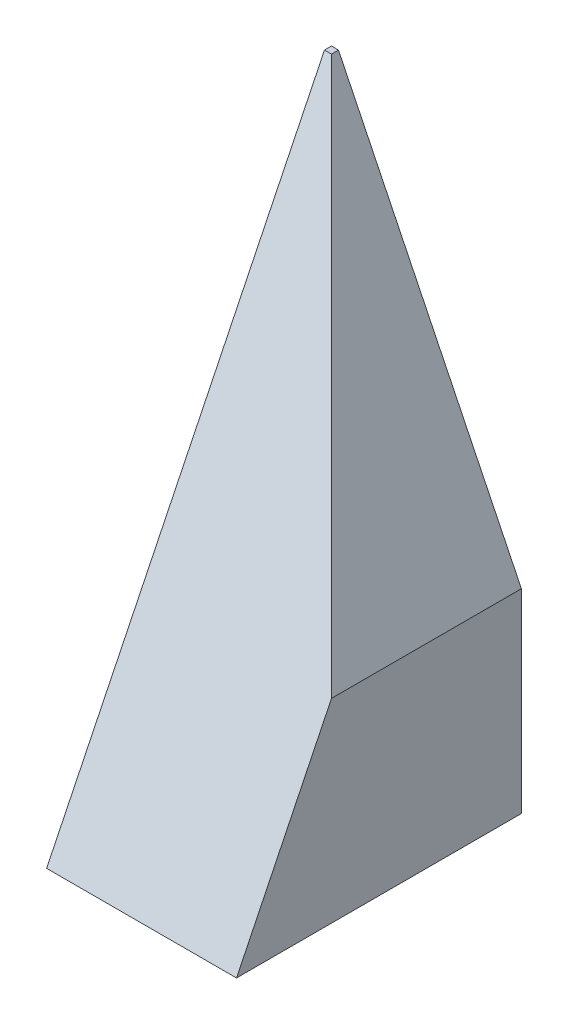
SolidWorks part; units mm, degrees
ref_plane "Front" through (0, 0, 0) normal (0, 0, 1) x (1, 0, 0)
ref_plane "Top" through (0, 0, 0) normal (0, 1, 0) x (1, 0, 0)
ref_plane "Right" through (0, 0, 0) normal (1, 0, 0) x (0, 0, -1)
sketch "Sketch1" plane through (0, 0, 0) normal (0, 1, 0) x (1, 0, 0)
  line L1 (0, 0) -> (30, 0)
  line L2 (0, 0) -> (0, -30)
  line L3 (0, -30) -> (30, -30)
  line L4 (30, 0) -> (30, -30)
extrude "Boss-Extrude1" add sketch "Sketch1" along normal blind 60
chamfer "Chamfer1" distance 60 angle 26 2 edges at (30, 60, 15) (15, 60, 30) first distance on face at (30, 30, 15) first distance on face at (15, 30, 30)
sketch "Sketch2" plane through (0, 0, 0) normal (0, 1, 0) x (1, 0, 0)
  line L0 (-16.5, 0) -> (16.5, 0) construction
  line L1 (30, 0) -> (20, 0)
  line L2 (30, 0) -> (30, -30)
  line L3 (30, -30) -> (20, -30)
  line L4 (20, 0) -> (20, -30)
  line L5 (30, -30) -> (30, 0) construction
  line L6 (0, -30) -> (30, -30) construction
  dimension "D1" = 10
extrude "Cut-Extrude1" cut sketch "Sketch2" along normal blind 101
